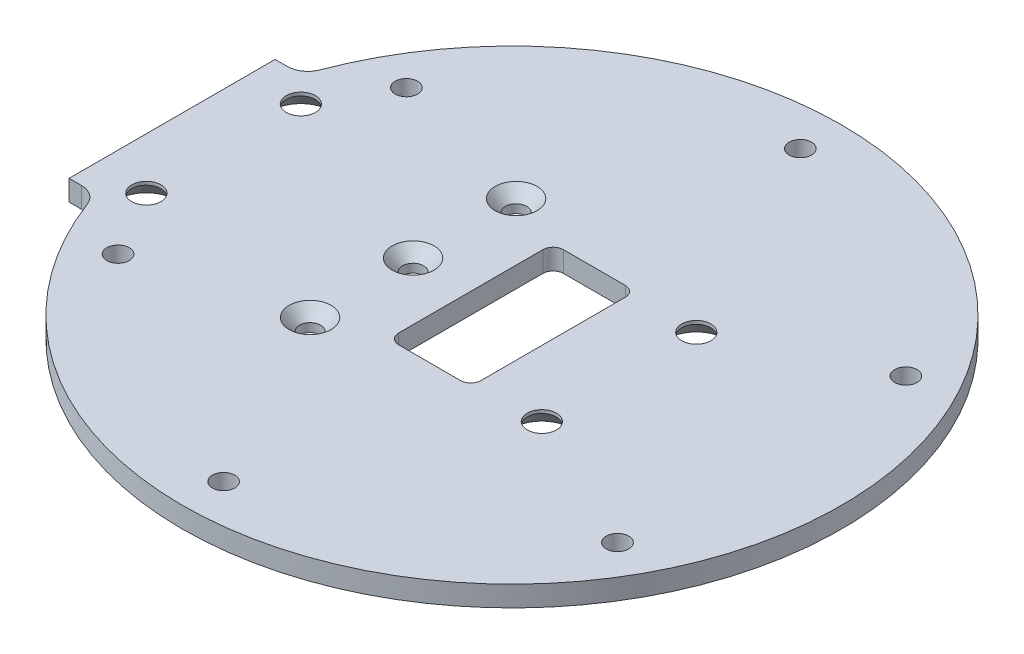
SolidWorks part; units mm, degrees
material "6061-T6 (SS)"
ref_plane "Front Plane" through (0, 0, 0) normal (0, 0, 1) x (1, 0, 0)
ref_plane "Top Plane" through (0, 0, 0) normal (0, 1, 0) x (1, 0, 0)
ref_plane "Right Plane" through (0, 0, 0) normal (1, 0, 0) x (0, 0, -1)
sketch "Sketch1" plane through (0, 0, 0) normal (0, 1, 0) x (1, 0, 0)
  circle A0 centre (0, 0) radius 50.8
  dimension "D1" = 101.6
extrude "Boss-Extrude1" add sketch "Sketch1" along normal blind 3.175
sketch "Sketch8" plane through (0, 0, 0) normal (0, -1, 0) x (1, 0, 0)
  line L1 (-48.2558, -15.875) -> (-52.3875, -15.875)
  line L3 (-48.2558, 15.875) -> (-52.3875, 15.875)
  line L4 (-52.3875, -15.875) -> (-52.3875, 15.875)
  line L5 (-18.5577, -15.875) -> (-52.3875, 15.875) construction
  line L6 (-18.5577, 15.875) -> (-52.3875, -15.875) construction
  circle A0 centre (0, 0) radius 50.8 construction
  circle A1 centre (0, 0) radius 50.8
  point P0 (-35.4726, 0)
  circle M3 centre (0, 0) radius 50.8
  dimension "D1" = 31.75
  dimension "D2" = 52.3875
extrude "Boss-Extrude2" add sketch "Sketch8" against normal up to surface (3.175 mm away) contours L4 L3 M3 | L4 L1 M3 region at (-51.0564, 0, 0) up to face at (0, 3.175, 50.8)
fillet "Fillet1" radius 3.175 2 edges at (-48.2558, 1.5875, -15.875) (-48.2558, 1.5875, 15.875)
hole_wizard "CSK for #8 Flat Head Socket Cap Screw1" positions "Sketch7" profile "Sketch6" countersink size "#8" standard "Ansi Inch" end condition through all
sketch "Sketch7" plane through (0, 0, 0) normal (0, -1, 0) x (1, 0, 0)
  line L2 (0, 0) -> (-50.8, 0) construction
  circle A0 centre (0, 0) radius 50.8 construction
  point P0 (-44.45, 11.9062)
  point P1 (-44.45, -11.9063)
  point P22 (16.51, -11.9063)
  point P24 (16.51, 11.9062)
  dimension "D1" = 23.8125
  dimension "D2" = 11.9062
  dimension "D3" = 6.35
  dimension "D4" = 60.96
sketch "Sketch6" plane through (-44.45, 0, 11.9062) normal (1, 0, 0) x (0, 0, -1)
  line L0 (0, 0) -> (0, 3.175)
  line L1 (0, 3.175) -> (2.2479, 3.175)
  line L2 (2.2479, 3.175) -> (2.2479, 2.659)
  line L3 (2.2479, 2.659) -> (4.5593, 0)
  line L5 (4.5593, 0) -> (0, 0)
  line L6 (-2.2479, 2.659) -> (-4.5593, 0) construction
  line L11 (0, -6.35) -> (0, 107.95) construction
  dimension "Thru Hole Dia." = 4.4958
  dimension "Thru Hole Depth" = 3.175
  dimension "Near C'Sink Dia." = 9.1186
  dimension "Near C'Sink Angle" = 82
hole_wizard "#8-32 Tapped Hole1" positions "Sketch11" profile "Sketch10" tap size "#8-32" standard "Ansi Inch"
sketch "Sketch11" plane through (0, 3.175, 0) normal (0, 1, 0) x (-1, 0, 0)
  point P0 (0, -44.45)
  dimension "D1" = 44.45
sketch "Sketch10" plane through (0, 3.175, -44.45) normal (1, 0, 0) x (0, 0, 1)
  line L0 (0, 0) -> (0, 11.7058)
  line L1 (0, 11.7058) -> (1.7272, 10.668)
  line L2 (1.7272, 10.668) -> (1.7272, 0)
  line L5 (1.7272, 0) -> (0, 0)
  line L10 (0, 11.7058) -> (-1.7272, 10.668) construction
  line L11 (0, -6.35) -> (0, 107.95) construction
  dimension "Tap Drill Dia." = 3.4544
  dimension "Tap Drill Depth" = 10.668
  dimension "Drill Angle" = 118
pattern_circular "CirPattern1" count 6 over 360 about axis through (0, 3.175, 0) along (0, 1, 0) of "#8-32 Tapped Hole1"
hole_wizard "CSK for #4 Flat Head Socket Cap Screw2" positions "Sketch16" profile "Sketch15" countersink size "#4" standard "Ansi Inch" end condition through all
sketch "Sketch16" plane through (0, 3.175, 0) normal (0, 1, 0) x (-1, 0, 0)
  point P0 (15.24, 0)
  point P1 (15.24, -15.875)
  point P3 (15.24, 15.875)
  dimension "D1" = 15.875
  dimension "D2" = 15.875
  dimension "D3" = 15.24
sketch "Sketch15" plane through (-15.24, 3.175, 0) normal (1, 0, 0) x (0, 0, 1)
  line L0 (0, 0) -> (0, 3.175)
  line L1 (0, 3.175) -> (1.6319, 3.175)
  line L2 (1.6319, 3.175) -> (1.6319, 1.8481)
  line L3 (1.6319, 1.8481) -> (3.2385, 0)
  line L5 (3.2385, 0) -> (0, 0)
  line L6 (-1.6319, 1.8481) -> (-3.2385, 0) construction
  line L11 (0, -6.35) -> (0, 107.95) construction
  dimension "Thru Hole Dia." = 3.2639
  dimension "Thru Hole Depth" = 3.175
  dimension "Near C'Sink Dia." = 6.477
  dimension "Near C'Sink Angle" = 82
sketch "Sketch17" plane through (0, 3.175, 0) normal (0, 1, 0) x (1, 0, 0)
  line L1 (6.35, 12.7) -> (-6.35, 12.7)
  line L2 (6.35, 12.7) -> (6.35, -12.7)
  line L3 (6.35, -12.7) -> (-6.35, -12.7)
  line L4 (-6.35, 12.7) -> (-6.35, -12.7)
  line L5 (6.35, 12.7) -> (-6.35, -12.7) construction
  line L6 (6.35, -12.7) -> (-6.35, 12.7) construction
  point P0 (0, 0)
  dimension "D1" = 25.4
  dimension "D2" = 12.7
extrude "Cut-Extrude2" cut sketch "Sketch17" against normal through all
fillet "Fillet2" radius 1.5875 4 edges at (-6.35, 1.5875, -12.7) (6.35, 1.5875, -12.7) (-6.35, 1.5875, 12.7) (6.35, 1.5875, 12.7)
